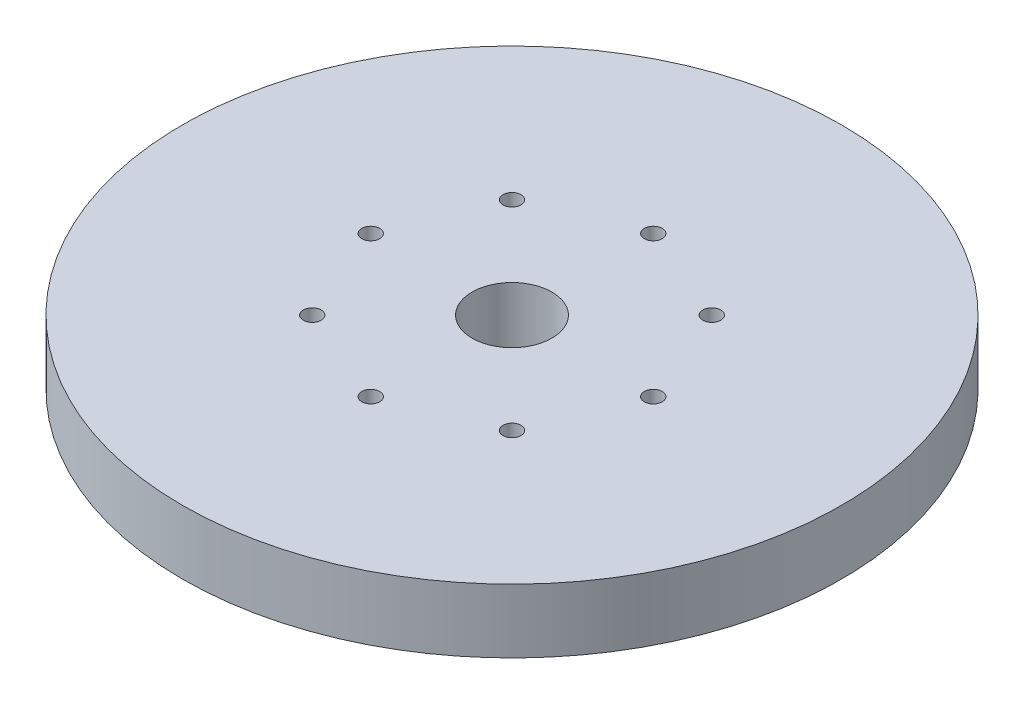
SolidWorks part; units mm, degrees
ref_plane "Front Plane" through (0, 0, 0) normal (0, 0, 1) x (1, 0, 0)
ref_plane "Top Plane" through (0, 0, 0) normal (0, 1, 0) x (1, 0, 0)
ref_plane "Right Plane" through (0, 0, 0) normal (1, 0, 0) x (0, 0, -1)
sketch "Sketch1" plane through (0, 0, 0) normal (0, 1, 0) x (1, 0, 0)
  circle A0 centre (0, 0) radius 82.5
  dimension "FLANGE_OD" = 165
extrude "Boss-Extrude1" add sketch "Sketch1" along normal blind 16
sketch "Sketch2" plane through (0, 0, 0) normal (0, 1, 0) x (1, 0, 0)
  circle A0 centre (0, 0) radius 10
  dimension "BORE_D" = 20
extrude "Cut-Extrude1" cut sketch "Sketch2" along normal through all
sketch "Sketch3" plane through (0, 16, 0) normal (0, 1, 0) x (1, 0, 0)
  circle A0 centre (0, 0) radius 35.3605 construction
  circle A1 centre (-35.3605, 0) radius 2.2435
  dimension "BOLT_D" = 4.487
  dimension "BOLT_PCD" = 70.721
extrude "Cut-Extrude2" cut sketch "Sketch3" against normal blind 10.9811
pattern_circular "CirPattern1" count 8 over 360 about axis through (0, 0, 0) along (0, 1, 0) of "Cut-Extrude2"
